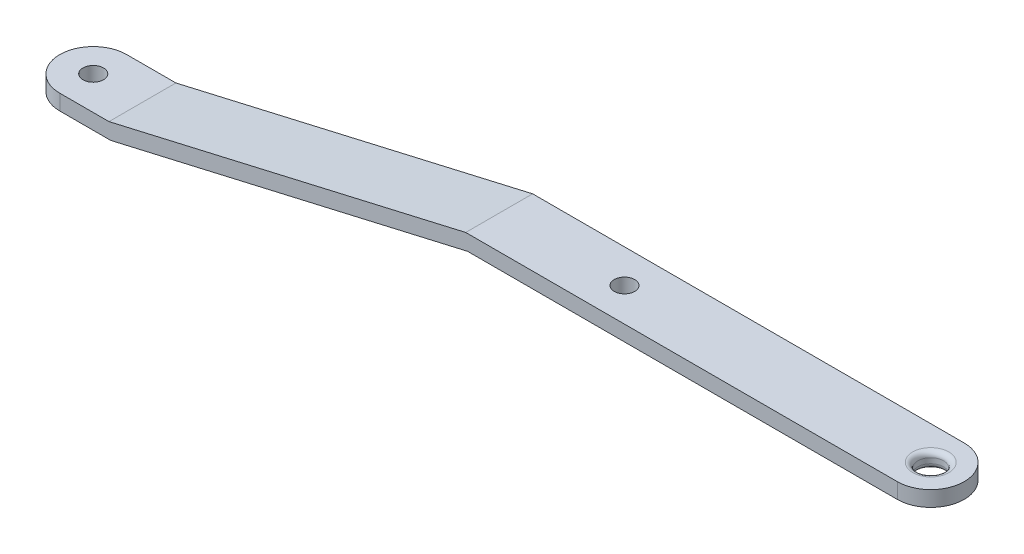
SolidWorks part; units mm, degrees
ref_plane "Front Plane" through (0, 0, 0) normal (0, 0, 1) x (1, 0, 0)
ref_plane "Top Plane" through (0, 0, 0) normal (0, 1, 0) x (1, 0, 0)
ref_plane "Right Plane" through (0, 0, 0) normal (1, 0, 0) x (0, 0, -1)
sketch "Sketch1" plane through (0, 0, 0) normal (0, 0, 1) x (1, 0, 0)
  line L0 (-82, 0) -> (0, 0)
  line L1 (0, 0) -> (346.5181, 80)
  line L2 (346.5181, 80) -> (796.5181, 80)
  line L3 (-82, 15) -> (-1.709, 15)
  line L4 (-1.709, 15) -> (344.809, 95)
  line L5 (344.809, 95) -> (796.5181, 95)
  line L6 (-82, 15) -> (-82, 0)
  line L7 (796.5181, 95) -> (796.5181, 80)
  dimension "D1" = 82
  dimension "D2" = 450
  dimension "D3" = 13
  dimension "D4" = 80
  dimension "D5" = 15
extrude "Boss-Extrude1" add sketch "Sketch1" along normal blind 65
fillet "Fillet1" 2 edges at (-82, 7.5, 65) (-82, 7.5, 0) type full round first side face at (264.8318, 47.5, 65) second side face at (264.8318, 47.5, 0) middle face at (-82, 7.5, 32.5)
fillet "Fillet2" 2 edges at (796.5181, 87.5, 0) (796.5181, 87.5, 65) type full round first side face at (272.9568, 47.5, 0) second side face at (272.9568, 47.5, 65) middle face at (796.5181, 87.5, 32.5)
sketch "Sketch3" plane through (0, 80, 0) normal (0, -1, 0) x (1, 0, 0)
  line L0 (346.5181, 65) -> (346.5181, 0) construction
  line L1 (346.5181, 65) -> (764.0181, 65) construction
  circle A0 centre (466.5181, 32.5) radius 10
  dimension "D1" = 20
  dimension "D2" = 120
  dimension "D3" = 32.5
extrude "Cut-Extrude1" cut sketch "Sketch3" against normal blind 20
sketch "Sketch4" plane through (0, 0, 0) normal (0, -1, 0) x (1, 0, 0)
  circle A0 centre (-49.5, 32.5) radius 10
  dimension "D1" = 20
extrude "Cut-Extrude2" cut sketch "Sketch4" against normal blind 20
sketch "Sketch5" plane through (0, 80, 0) normal (0, -1, 0) x (1, 0, 0)
  circle A0 centre (764.0181, 32.5) radius 12.5
  dimension "D1" = 25
extrude "Cut-Extrude3" cut sketch "Sketch5" against normal blind 20
fillet "Fillet3" radius 5 2 edges at (764.0181, 95, 20) (764.0181, 80, 20)
